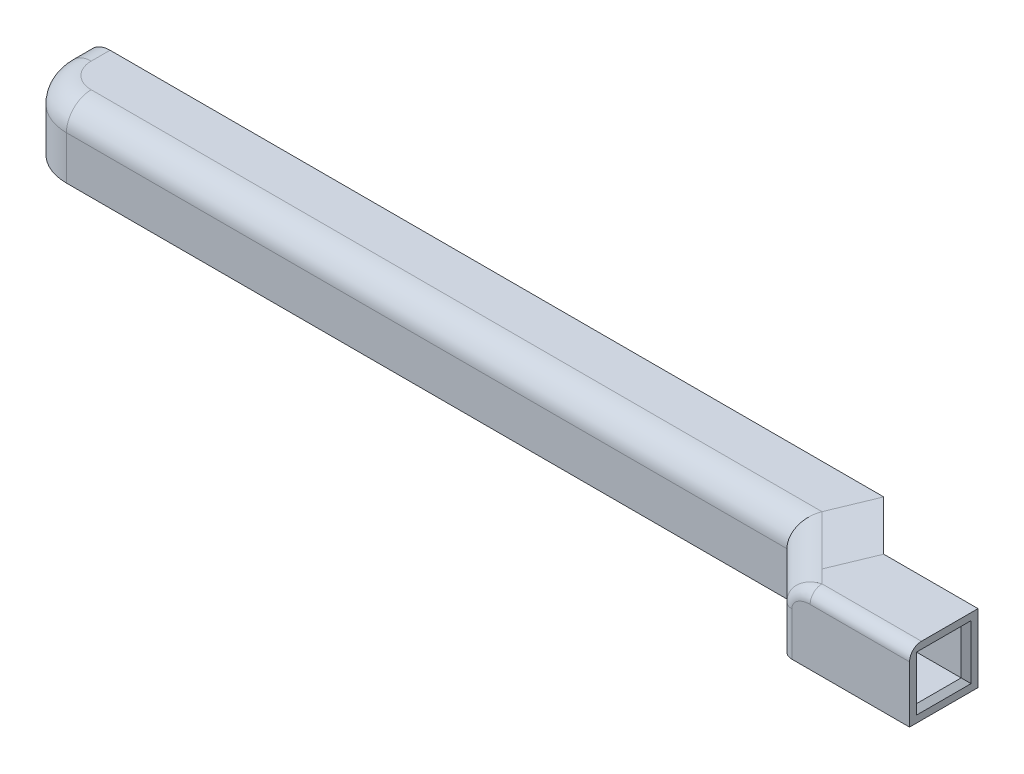
SolidWorks part; units mm, degrees
ref_plane "Front Plane" through (0, 0, 0) normal (0, 0, 1) x (1, 0, 0)
ref_plane "Top Plane" through (0, 0, 0) normal (0, 1, 0) x (1, 0, 0)
ref_plane "Right Plane" through (0, 0, 0) normal (1, 0, 0) x (0, 0, -1)
sketch "Sketch1" plane through (0, 0, 0) normal (1, 0, 0) x (0, 0, -1)
  line L0 (-2.4, 11.4) -> (11.4, 11.4)
  line L1 (0, 0) -> (9, 0)
  line L2 (0, 0) -> (0, 9)
  line L3 (0, 9) -> (9, 9)
  line L4 (9, 0) -> (9, 9)
  line L5 (11.4, -2.4) -> (11.4, 11.4)
  line L6 (-2.4, -2.4) -> (11.4, -2.4)
  line L7 (-2.4, -2.4) -> (-2.4, 11.4)
  dimension "D1" = 9
  dimension "D2" = 2.4
sketch "Sketch2" plane through (0, 0, 0) normal (0, 1, 0) x (1, 0, 0)
  line L1 (0, 9) -> (-20, 9)
  line L2 (-20, 9) -> (-20, 19) construction
  line L3 (-20, 19) -> (-30, 19) construction
  line L4 (-20, 9) -> (-30, 19)
  line L5 (-30, 19) -> (-190, 19)
  dimension "D2" = 10
  dimension "D3" = 160
  dimension "D4" = 20
sweep "Sweep1" add profiles "Sketch1" path "Sketch2"
sketch "Sketch6" plane through (-190, 0, 0) normal (-1, 0, 0) x (0, 0, 1)
  line L1 (-10, 9) -> (-19, 9)
  line L2 (-10, 9) -> (-10, 0)
  line L3 (-10, 0) -> (-19, 0)
  line L4 (-19, 9) -> (-19, 0)
extrude "Boss-Extrude1" add sketch "Sketch6" against normal up to next
fillet "Fillet1" radius 10 1 edges at (-190, 4.5, -7.6)
fillet "Fillet2" radius 5 4 edges at (-190, 11.4, -19.5) (-187.0711, 11.4, -10.5289) (-29.722, 11.4, -2.6) (-107.361, 11.4, -7.6)
fillet "Fillet3" radius 2.4 3 edges at (-8.8255, 11.4, 2.4) (-22.651, 9.9355, 2.4) (-24.722, 2, 2.4)
sketch "Sketch7" plane through (0, 0, -9) normal (0, 0, 1) x (1, 0, 0)
  line L1 (-8.2, 6.75) -> (-12.7, 6.75)
  line L2 (-8.2, 6.75) -> (-8.2, 2.25)
  line L3 (-8.2, 2.25) -> (-12.7, 2.25)
  line L4 (-12.7, 6.75) -> (-12.7, 2.25)
  line L5 (-10.45, 6.75) -> (-10.45, 9) construction
  line L7 (-10.45, 2.25) -> (-10.45, 0) construction
  line L9 (0, 9) -> (-20, 9) construction
  line L10 (0, 0) -> (-20, 0) construction
  line L11 (0, 9) -> (0, 0) construction
  dimension "D1" = 4.5
  dimension "D2" = 8.2
extrude "Cut-Extrude1" cut sketch "Sketch7" against normal up to next contours L2 L1 L4 L3
chamfer "Chamfer1" distance 1 angle 45 4 edges at (0, 4.5, -9) (0, 9, -4.5) (0, 4.5, 0) (0, 0, -4.5)
equation "\"Tube_ID\"= 9"
equation "\"D1@Sketch1\"=\"Tube_ID\""
equation "\"wall_Thickness\"=2.4"
equation "\"D2@Sketch1\"=\"wall_Thickness\""
equation "\"Extension_Length\"= 160"
equation "\"D3@Sketch2\"=\"Extension_Length\""
equation "\"Offset_Amount\"=10"
equation "\"D2@Sketch2\"=\"Offset_Amount\""
equation "\"Socket_Depth\"=20"
equation "\"D4@Sketch2\"=\"Socket_Depth\""
equation "\"Overall_Length\"= \"Extension_Length\" + \"Offset_Amount\" + \"Socket_Depth\""
